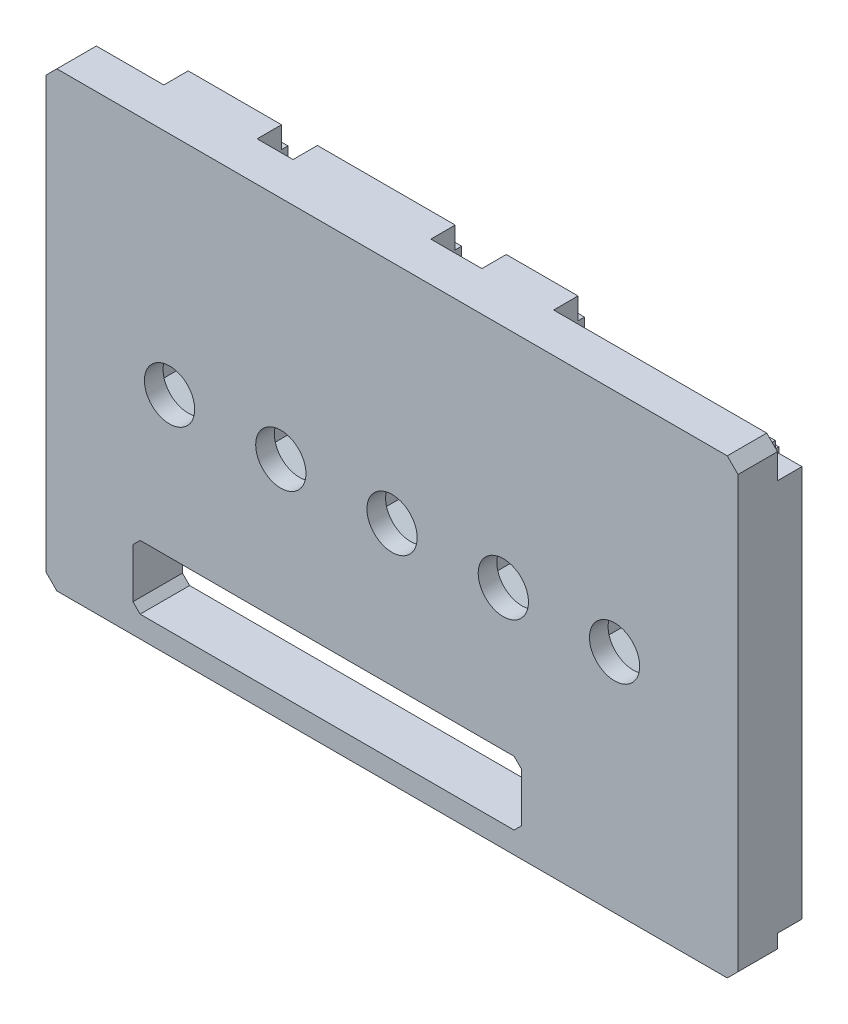
SolidWorks part; units mm, degrees
ref_plane "Front Plane" through (0, 0, 0) normal (0, 0, 1) x (1, 0, 0)
ref_plane "Top Plane" through (0, 0, 0) normal (0, 1, 0) x (1, 0, 0)
ref_plane "Right Plane" through (0, 0, 0) normal (1, 0, 0) x (0, 0, -1)
sketch "Sketch1" plane through (0, 0, 0) normal (0, 0, 1) x (1, 0, 0)
  line L1 (-38.1418, 30.0688) -> (58.2582, 30.0688)
  line L2 (-38.1418, 30.0688) -> (-38.1418, -32.9312)
  line L3 (-38.1418, -32.9312) -> (58.2582, -32.9312)
  line L4 (58.2582, 30.0688) -> (58.2582, -32.9312)
  line L5 (-36.4418, 28.3688) -> (56.5582, 28.3688)
  line L6 (-36.4418, 28.3688) -> (-36.4418, -31.2312)
  line L7 (-36.4418, -31.2312) -> (56.5582, -31.2312)
  line L8 (56.5582, 28.3688) -> (56.5582, -31.2312)
  line L9 (-31.6418, 27.0688) -> (55.2582, 27.0688)
  line L10 (-31.6418, 27.0688) -> (-31.6418, -29.9312)
  line L11 (-31.6418, -29.9312) -> (55.2582, -29.9312)
  line L12 (55.2582, 27.0688) -> (55.2582, -29.9312)
  dimension "D1" = 96.4
  dimension "D2" = 63
  dimension "D3" = 3
  dimension "D4" = 6.5
  dimension "D5" = 4.8
  dimension "D6" = 1.3
  dimension "D7" = 1.3
  dimension "D8" = 3
  dimension "D9" = 3
  dimension "D10" = 1.3
extrude "Boss-Extrude1" add sketch "Sketch1" along normal blind 5.5 contours L1 L4 L3 L2
extrude "Boss-Extrude2" add sketch "Sketch1<5>" against normal blind 1.4 contours L12 L9 L10 L11 | L8 L5 L6 L7 L9 L12 L11 L10 region at (10.0582, 27.2643, 0) region at (11.8082, -1.4312, 0)
sketch "Sketch1<5>" plane through (0, 0, 0) normal (0, 0, 1) x (1, 0, 0) same geometry as "Sketch1"
chamfer "Chamfer1" distance 1.5 angle 45 4 edges at (58.2582, 30.0688, 2.75) (-38.1418, 30.0688, 2.75) (-38.1418, -32.9312, 2.75) (58.2582, -32.9312, 2.75)
sketch "Sketch3" plane through (0, 0, -1.4) normal (0, 0, -1) x (-1, 0, 0)
  line L0 (36.4418, 28.3688) -> (36.4418, 28.1688)
  line L1 (36.4418, 28.3688) -> (36.4418, -31.2312) construction
  line L2 (36.4418, 28.1688) -> (36.4418, 5.3688)
  line L3 (36.4418, 5.3688) -> (36.4418, 4.9688)
  line L4 (36.4418, 4.9688) -> (38.1418, 4.9688)
  line L5 (38.1418, 4.9688) -> (38.1418, -8.2312)
  line L6 (38.1418, 28.5688) -> (38.1418, -31.4312) construction
  line L7 (36.4418, -8.2312) -> (36.4418, 4.9688)
  line L8 (36.6418, -32.9312) -> (-56.7582, -32.9312) construction
  line L9 (38.1418, 4.9688) -> (35.1418, 4.9688)
  line L10 (38.1418, 4.9688) -> (38.1418, -8.2312)
  line L11 (38.1418, -8.2312) -> (35.1418, -8.2312)
  line L12 (35.1418, 4.9688) -> (35.1418, -8.2312)
  line M5 (36.4418, -31.2312) -> (36.4418, 28.3688)
  dimension "D1" = 0.2
  dimension "D2" = 22.8
  dimension "D3" = 0.4
  dimension "D4" = 13.2
  dimension "D5" = 24.7
extrude "Boss-Extrude4" add sketch "Sketch3" against normal blind 1.7 contours L5 L4 M5 region at (-37.2918, -1.6312, -1.4)
sketch "Sketch4" plane through (0, 0, -1.4) normal (0, 0, -1) x (-1, 0, 0)
  line L0 (36.4418, 28.3688) -> (27.2418, 28.3688)
  line L1 (36.4418, 28.3688) -> (-56.5582, 28.3688) construction
  line L2 (27.2418, 28.3688) -> (14.2418, 28.3688)
  line L3 (14.2418, 28.3688) -> (9.2418, 28.3688)
  line L4 (9.2418, 28.3688) -> (-9.9582, 28.3688)
  line L5 (-9.9582, 28.3688) -> (-17.0682, 28.3688)
  line L6 (-17.0682, 28.3688) -> (-27.0682, 28.3688)
  line L8 (36.6418, 30.0688) -> (-56.7582, 30.0688) construction
  line L9 (-27.0682, 28.3688) -> (-17.0682, 28.3688)
  line L10 (-27.0682, 28.3688) -> (-27.0682, 30.0688)
  line L11 (-27.0682, 30.0688) -> (-17.0682, 30.0688)
  line L12 (-17.0682, 28.3688) -> (-17.0682, 30.0688)
  line L13 (-27.0682, 30.0688) -> (-17.0682, 30.0688)
  line L14 (-9.9582, 28.3688) -> (9.2418, 28.3688)
  line L15 (-9.9582, 28.3688) -> (-9.9582, 30.0688)
  line L16 (-9.9582, 30.0688) -> (9.2418, 30.0688)
  line L17 (9.2418, 28.3688) -> (9.2418, 30.0688)
  line L18 (14.2418, 28.3688) -> (27.2418, 28.3688)
  line L19 (14.2418, 28.3688) -> (14.2418, 30.0688)
  line L20 (14.2418, 30.0688) -> (27.2418, 30.0688)
  line L21 (27.2418, 28.3688) -> (27.2418, 30.0688)
  line L22 (-27.0682, 30.0688) -> (-27.0682, 27.0688)
  line L23 (-27.0682, 27.0688) -> (-17.0682, 27.0688)
  line L24 (-17.0682, 30.0688) -> (-17.0682, 27.0688)
  line L25 (-9.9582, 30.0688) -> (9.2418, 30.0688)
  line L26 (-9.9582, 30.0688) -> (-9.9582, 27.0688)
  line L27 (-9.9582, 27.0688) -> (9.2418, 27.0688)
  line L28 (9.2418, 30.0688) -> (9.2418, 27.0688)
  line L29 (14.2418, 30.0688) -> (27.2418, 30.0688)
  line L30 (14.2418, 30.0688) -> (14.2418, 27.0688)
  line L31 (14.2418, 27.0688) -> (27.2418, 27.0688)
  line L32 (27.2418, 30.0688) -> (27.2418, 27.0688)
  line M14 (36.4418, 28.3688) -> (-56.5582, 28.3688)
  dimension "D1" = 9.2
  dimension "D2" = 13
  dimension "D3" = 5
  dimension "D4" = 19.2
  dimension "D5" = 7.11
  dimension "D6" = 10
  dimension "D7" = 1.7
  dimension "D8" = 3
  dimension "D9" = 63.51
extrude "Boss-Extrude5" add sketch "Sketch4" against normal blind 1.6 contours L12 L11 L10 M14 | L17 L16 L15 M14 | L21 L20 L19 M14 region at (-20.7418, 29.2188, -1.4) region at (22.0682, 29.2188, -1.4) region at (0.3582, 29.2188, -1.4)
extrude "Boss-Extrude6" add sketch "Sketch4<3>" along normal blind 2 contours L12 L11 L10 M14 | L24 L22 L23 M14 | L28 L26 L27 M14 | L17 L16 L15 M14 | L32 L30 L31 M14 | L21 L20 L19 M14 region at (-20.7418, 27.7188, -1.4) region at (-20.7418, 29.2188, -1.4) region at (22.0682, 27.7188, -1.4) region at (22.0682, 29.2188, -1.4) region at (0.3582, 27.7188, -1.4) region at (0.3582, 29.2188, -1.4)
sketch "Sketch4<3>" plane through (0, 0, -1.4) normal (0, 0, -1) x (-1, 0, 0) same geometry as "Sketch4"
extrude "Boss-Extrude7" add sketch "Sketch3<5>" along normal blind 1 contours L9 L12 L11 M5 | L5 L4 M5 region at (-37.2918, -1.6312, -1.4) region at (-35.7918, -1.6312, -1.4)
sketch "Sketch3<5>" plane through (0, 0, -1.4) normal (0, 0, -1) x (-1, 0, 0) same geometry as "Sketch3"
sketch "Sketch5" plane through (0, 0, -1.4) normal (0, 0, -1) x (-1, 0, 0)
  line L0 (-56.5582, -32.9312) -> (-56.5582, -29.5312)
  line L1 (36.6418, -32.9312) -> (-56.7582, -32.9312) construction
  line L2 (-58.2582, -29.5312) -> (-56.5582, -29.5312)
  line L3 (-58.2582, 28.5688) -> (-58.2582, -31.4312) construction
  line L4 (-56.5582, -29.5312) -> (-56.5582, 25.0688)
  line L5 (-56.5582, 28.3688) -> (-56.5582, -31.2312) construction
  line L6 (-58.2582, -29.5312) -> (-55.2582, -29.5312)
  line L7 (-58.2582, -29.5312) -> (-56.5582, -29.5312)
  line L8 (-58.2582, -29.5312) -> (-58.2582, 25.0688)
  line L9 (-58.2582, 25.0688) -> (-56.5582, 25.0688)
  line L10 (-56.5582, -29.5312) -> (-56.5582, 25.0688)
  line L12 (-55.2582, -29.5312) -> (-58.2582, -29.5312)
  line L13 (-55.2582, -29.5312) -> (-55.2582, 25.0688)
  line L14 (-55.2582, 25.0688) -> (-58.2582, 25.0688)
  line L15 (-58.2582, -29.5312) -> (-58.2582, 25.0688)
  line M19 (-56.5582, 28.3688) -> (-56.5582, -31.2312)
  dimension "D1" = 3.4
  dimension "D2" = 54.6
extrude "Boss-Extrude8" add sketch "Sketch5" against normal blind 1.6 contours L9 L8 L2 M19 region at (57.4082, -2.2312, -1.4)
extrude "Boss-Extrude9" add sketch "Sketch5<3>" along normal blind 2 contours L13 L14 L6 M19 | L9 L8 L2 M19 region at (57.4082, -2.2312, -1.4) region at (55.9082, -2.2312, -1.4)
sketch "Sketch5<3>" plane through (0, 0, -1.4) normal (0, 0, -1) x (-1, 0, 0) same geometry as "Sketch5"
sketch "Sketch7" plane through (0, 0, 5.5) normal (0, 0, 1) x (1, 0, 0)
  line L0 (-36.6418, -32.9312) -> (56.7582, -32.9312) construction
  line L1 (-38.1418, -32.9312) -> (-26.0418, -32.9312)
  line L2 (-38.1418, -32.9312) -> (-38.1418, -29.9312)
  line L3 (-38.1418, -29.9312) -> (-26.0418, -29.9312)
  line L4 (-26.0418, -32.9312) -> (-26.0418, -29.9312)
  line L5 (-26.0418, -29.9312) -> (28.0582, -29.9312)
  line L6 (-26.0418, -29.9312) -> (-26.0418, -21.0312)
  line L7 (-26.0418, -21.0312) -> (28.0582, -21.0312)
  line L8 (28.0582, -29.9312) -> (28.0582, -21.0312)
  point P7 (-38.1418, -31.4312)
  point P8 (28.0582, -25.4812)
  dimension "D1" = 12.1
  dimension "D2" = 3
  dimension "D3" = 66.2
  dimension "D4" = 11.9
extrude "Cut-Extrude2" cut sketch "Sketch7" against normal blind 12 contours L5 L8 L7 L6 region at (1.0082, -25.4812, 5.5)
chamfer "Chamfer2" distance 1 angle 45 4 edges at (28.0582, -21.0312, 2.05) (28.0582, -29.9312, 2.05) (-26.0418, -29.9312, 2.05) (-26.0418, -21.0312, 2.05)
sketch "Sketch11" plane through (0, 27.0688, 0) normal (0, -1, 0) x (1, 0, 0)
  line L1 (17.0682, -3.4) -> (27.0682, -3.4)
  line L2 (17.0682, -3.4) -> (17.0682, -1.4)
  line L3 (17.0682, -1.4) -> (27.0682, -1.4)
  line L4 (27.0682, -3.4) -> (27.0682, -1.4)
  line L5 (-9.2418, -3.4) -> (9.9582, -3.4)
  line L6 (-9.2418, -3.4) -> (-9.2418, -1.4)
  line L7 (-9.2418, -1.4) -> (9.9582, -1.4)
  line L8 (9.9582, -3.4) -> (9.9582, -1.4)
  line L9 (-27.2418, -3.4) -> (-14.2418, -3.4)
  line L10 (-27.2418, -3.4) -> (-27.2418, -1.4)
  line L11 (-27.2418, -1.4) -> (-14.2418, -1.4)
  line L12 (-14.2418, -3.4) -> (-14.2418, -1.4)
extrude "Boss-Extrude10" add sketch "Sketch11" along normal blind 2
sketch "Sketch13" plane through (0, 0, -3.4) normal (0, 0, -1) x (-1, 0, 0)
  line L0 (-27.0682, 25.0688) -> (-27.0682, 28.3688) construction
  line L1 (-17.0682, 25.0688) -> (-27.0682, 25.0688)
  line L2 (-17.0682, 25.0688) -> (-17.0682, 27.0688)
  line L3 (-17.0682, 27.0688) -> (-27.0682, 27.0688)
  line L4 (-27.0682, 25.0688) -> (-27.0682, 27.0688)
  line L5 (-9.9582, 30.0688) -> (-9.9582, 25.0688) construction
  line L6 (9.2418, 25.0688) -> (-9.9582, 25.0688)
  line L7 (9.2418, 25.0688) -> (9.2418, 27.0688)
  line L8 (9.2418, 27.0688) -> (-9.9582, 27.0688)
  line L9 (-9.9582, 25.0688) -> (-9.9582, 27.0688)
  line L10 (14.2418, 28.3688) -> (14.2418, 25.0688) construction
  line L11 (27.2418, 25.0688) -> (14.2418, 25.0688)
  line L12 (27.2418, 25.0688) -> (27.2418, 27.0688)
  line L13 (27.2418, 27.0688) -> (14.2418, 27.0688)
  line L14 (14.2418, 25.0688) -> (14.2418, 27.0688)
extrude "Boss-Extrude12" add sketch "Sketch13" along normal blind 0.9
sketch "Sketch14" plane through (0, 0, -1.4) normal (0, 0, -1) x (-1, 0, 0)
  line L1 (-28.0582, -21.0312) -> (26.0418, -21.0312)
  line L2 (-28.0582, -21.0312) -> (-28.0582, -18.0312)
  line L3 (-28.0582, -18.0312) -> (26.0418, -18.0312)
  line L4 (26.0418, -21.0312) -> (26.0418, -18.0312)
extrude "Boss-Extrude13" add sketch "Sketch14" along normal blind 2.9
sketch "Sketch15" plane through (55.2582, 0, 0) normal (-1, 0, 0) x (0, 0, 1)
  line L1 (-3.4, 25.0688) -> (-1.4, 25.0688)
  line L2 (-3.4, 25.0688) -> (-3.4, -29.5312)
  line L3 (-3.4, -29.5312) -> (-1.4, -29.5312)
  line L4 (-1.4, 25.0688) -> (-1.4, -29.5312)
extrude "Boss-Extrude14" add sketch "Sketch15" along normal blind 4.5
sketch "Sketch16" plane through (0, 0, -3.4) normal (0, 0, -1) x (-1, 0, 0)
  line L0 (-50.7582, 25.0688) -> (-58.2582, 25.0688) construction
  line L1 (-50.7582, -29.5312) -> (-54.2582, -29.5312)
  line L2 (-50.7582, -29.5312) -> (-50.7582, 25.0688)
  line L3 (-50.7582, 25.0688) -> (-54.2582, 25.0688)
  line L4 (-54.2582, -29.5312) -> (-54.2582, 25.0688)
extrude "Boss-Extrude15" add sketch "Sketch16" along normal blind 0.8
sketch "Sketch18" plane through (0, 0, -1.4) normal (0, 0, -1) x (-1, 0, 0)
  line L0 (-41.0582, -1.4312) -> (-58.2582, -1.4312)
  line L1 (-58.2582, -29.5312) -> (-58.2582, 25.0688) construction
  line L2 (-41.0582, -1.4312) -> (-25.5582, -1.4312)
  line L3 (-25.5582, -1.4312) -> (-10.0582, -1.4312)
  line L4 (-10.0582, -1.4312) -> (5.4418, -1.4312)
  line L5 (5.4418, -1.4312) -> (20.9418, -1.4312)
  line L6 (20.9418, -1.4312) -> (38.1418, -1.4312)
  line L7 (-41.0582, -1.4312) -> (-41.0582, 30.0688)
  line L8 (-41.0582, -8.0707) -> (-35.3082, -4.7509)
  line L9 (-35.3082, -4.7509) -> (-35.3082, 1.8886)
  line L10 (-35.3082, 1.8886) -> (-41.0582, 5.32)
  line L11 (-41.0582, 5.32) -> (-46.8082, 1.8886)
  line L12 (-46.8082, 1.8886) -> (-46.8082, -4.7509)
  line L13 (-46.8082, -4.7509) -> (-41.0582, -8.0707)
  line L14 (-25.5582, 5.2084) -> (-31.3082, 1.8886)
  line L15 (-31.3082, 1.8886) -> (-31.3082, -4.7509)
  line L16 (-31.3082, -4.7509) -> (-25.5582, -8.0707)
  line L17 (-25.5582, -8.0707) -> (-19.8082, -4.7509)
  line L18 (-19.8082, -4.7509) -> (-19.8082, 1.8886)
  line L19 (-19.8082, 1.8886) -> (-25.5582, 5.2084)
  line L20 (-10.0582, 5.2084) -> (-15.8082, 1.8886)
  line L21 (-15.8082, 1.8886) -> (-15.8082, -4.7509)
  line L22 (-15.8082, -4.7509) -> (-10.0582, -8.0707)
  line L23 (-10.0582, -8.0707) -> (-4.3082, -4.7509)
  line L24 (-4.3082, -4.7509) -> (-4.3082, 1.8886)
  line L25 (-4.3082, 1.8886) -> (-10.0582, 5.2084)
  line L26 (5.4418, 5.2084) -> (-0.3082, 1.8886)
  line L27 (-0.3082, 1.8886) -> (-0.3082, -4.7509)
  line L28 (-0.3082, -4.7509) -> (5.4418, -8.0707)
  line L29 (5.4418, -8.0707) -> (11.1918, -4.7509)
  line L30 (11.1918, -4.7509) -> (11.1918, 1.8886)
  line L31 (11.1918, 1.8886) -> (5.4418, 5.2084)
  line L32 (20.9418, 5.2084) -> (15.1918, 1.8886)
  line L33 (15.1918, 1.8886) -> (15.1918, -4.7509)
  line L34 (15.1918, -4.7509) -> (20.9418, -8.0707)
  line L35 (20.9418, -8.0707) -> (26.6918, -4.7509)
  line L36 (26.6918, -4.7509) -> (26.6918, 1.8886)
  line L38 (38.1418, 4.9688) -> (38.1418, -8.2312) construction
  line L39 (26.6918, 1.8886) -> (20.9418, 5.2084)
  line L40 (-27.0682, 30.0688) -> (-56.7582, 30.0688) construction
  line L41 (-41.0582, -1.4312) -> (-41.0582, -32.9312)
  line L42 (36.6418, -32.9312) -> (-56.7582, -32.9312) construction
  circle A0 centre (-41.0582, -1.4312) radius 3.5
  circle A1 centre (-25.5582, -1.4312) radius 3.5
  circle A2 centre (-10.0582, -1.4312) radius 3.5
  circle A3 centre (5.4418, -1.4312) radius 3.5
  circle A4 centre (20.9418, -1.4312) radius 3.5
  circle A5 centre (-41.0582, -1.4312) radius 5.75 construction
  circle A6 centre (-25.5582, -1.4312) radius 5.75 construction
  circle A7 centre (-10.0582, -1.4312) radius 5.75 construction
  circle A8 centre (5.4418, -1.4312) radius 5.75 construction
  circle A9 centre (20.9418, -1.4312) radius 5.75 construction
  dimension "D6" = 11.5
  dimension "D1" = 15.5
  dimension "D2" = 15.5
  dimension "D3" = 15.5
  dimension "D4" = 15.5
extrude "Cut-Extrude4" cut sketch "Sketch18" against normal blind 12 contours A0 | A1 | A2 | A3 | A4
extrude "Cut-Extrude5" cut sketch "Sketch18<3>" against normal blind 4.3 contours L10 L11 L12 L13 L8 L9 | L19 L14 L15 L16 L17 L18 | L25 L20 L21 L22 L23 L24 | L31 L26 L27 L28 L29 L30 | L39 L32 L33 L34 L35 L36
sketch "Sketch18<3>" plane through (0, 0, -1.4) normal (0, 0, -1) x (-1, 0, 0) same geometry as "Sketch18"
